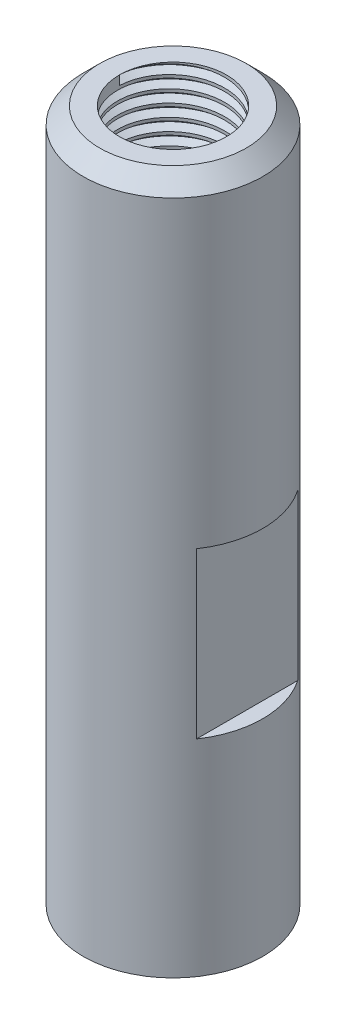
SolidWorks part; units mm, degrees
ref_plane "Front Plane" through (0, 0, 0) normal (0, 0, 1) x (1, 0, 0)
ref_plane "Top Plane" through (0, 0, 0) normal (0, 1, 0) x (1, 0, 0)
ref_plane "Right Plane" through (0, 0, 0) normal (1, 0, 0) x (0, 0, -1)
sketch "Sketch1" plane through (0, 0, 0) normal (0, 1, 0) x (1, 0, 0)
  circle A0 centre (0, 0) radius 10.9
  dimension "D1" = 21.8
extrude "Boss-Extrude1" add sketch "Sketch1" along normal up to surface (84 mm away)
sketch "Sketch2" plane through (0, 84, 0) normal (0, 1, 0) x (1, 0, 0)
  circle A0 centre (0, 0) radius 6.5
  dimension "D1" = 13
extrude "Cut-Extrude1" cut sketch "Sketch2" against normal blind 20
thread "Thread1" pitch 1.5 method cut profile "Thread Profile1" start angle 0, offset 0, length 26, pitch 1.5, diameter 13
ref_plane "Plane1" through (-6.5, 84, 0) normal (0, 0, 1) x (-1, 0, 0)
sketch "Thread Profile1" plane through (-6.5, 84, 0) normal (0, 0, 1) x (-1, 0, 0)
  line L0 (0, 0) -> (0, 1.5) construction
  line L1 (0, 0) -> (0.8119, 0.4687)
  line L2 (0.8119, 0.4687) -> (0.8119, 0.6562)
  line L3 (0.8119, 0.6562) -> (0, 1.125)
  line L4 (0.8119, 0.5625) -> (0, 0.5625) construction
  line L11 (0, 0) -> (0, 1.125)
  point P2 (0, 0)
  dimension "Pitch" = 1.5
  dimension "Profile_Angle" = 60
  dimension "Profile_Land" = 0.1875
  dimension "Profile_Height" = 0.8119
sketch "Sketch8" plane through (0, 0, 0) normal (0, -1, 0) x (1, 0, 0)
  circle A0 centre (0, 0) radius 7.5
  dimension "D1" = 15
sketch "Sketch23" plane through (0, 0, 0) normal (0, 0, 1) x (1, 0, 0)
  line L0 (-10.9, 84) -> (-10.9, 0) construction
  line L1 (-10.9, 25) -> (-9, 25)
  line L2 (-10.9, 25) -> (-10.9, 45)
  line L3 (-10.9, 45) -> (-9, 45)
  line L4 (-9, 25) -> (-9, 45)
  line L5 (10.9, 0) -> (10.9, 84) construction
  line L6 (10.9, 25) -> (9, 25)
  line L7 (10.9, 25) -> (10.9, 45)
  line L8 (10.9, 45) -> (9, 45)
  line L9 (9, 25) -> (9, 45)
  dimension "D1" = 20
  dimension "D2" = 25
  dimension "D3" = 18
  dimension "D4" = 1.9
  dimension "D5" = 1.9
extrude "Cut-Extrude2" cut sketch "Sketch23" against normal blind 16 and the other way blind 16
extrude "Cut-Extrude3" cut sketch "Sketch8" against normal up to surface (64 mm away) up to face at (4.436, 64, -1.2029)
chamfer "Chamfer1" distance 2 angle 45 1 edges at (0, 84, -10.9)
